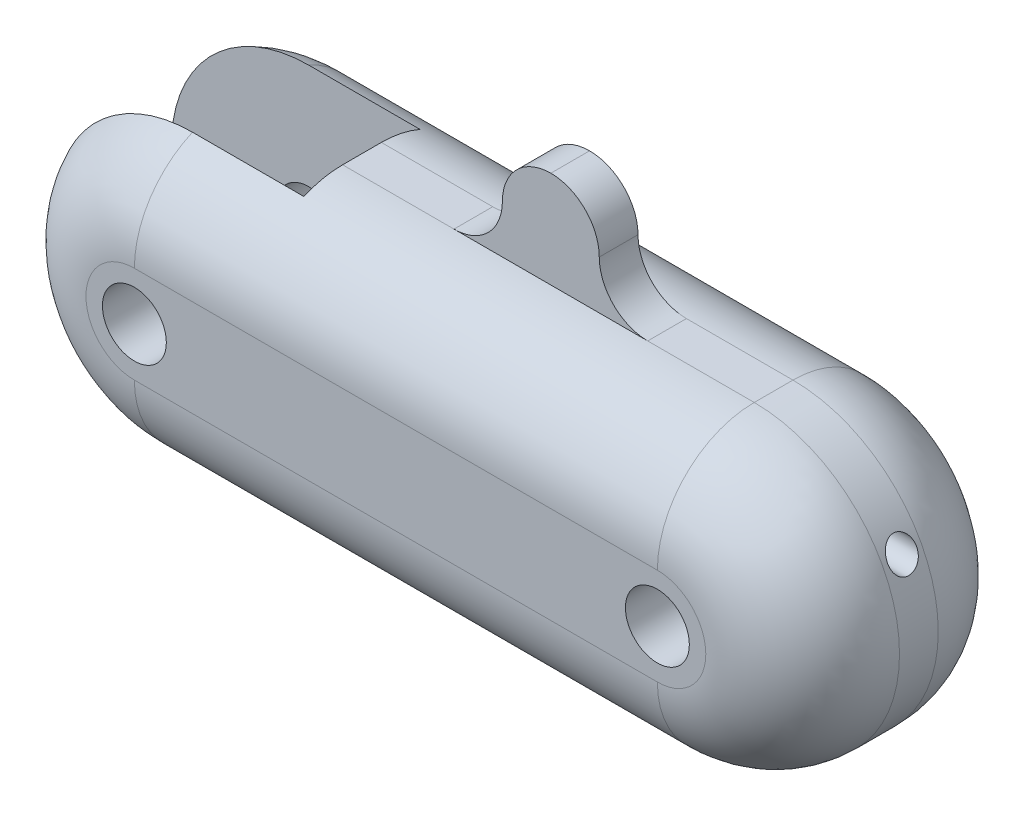
SolidWorks part; units mm, degrees
ref_plane "Front Plane" through (0, 0, 0) normal (0, 0, 1) x (1, 0, 0)
ref_plane "Top Plane" through (0, 0, 0) normal (0, 1, 0) x (1, 0, 0)
ref_plane "Right Plane" through (0, 0, 0) normal (1, 0, 0) x (0, 0, -1)
sketch "Sketch2" plane through (0, 0, 0) normal (0, 0, 1) x (1, 0, 0)
  line L0 (-13.5, 0) -> (13.5, 0)
  line L1 (-13.5, -15) -> (13.5, -15)
  arc A0 (-13.5, 0) -> (-13.5, -15) centre (-13.5, -7.5) ccw
  arc A1 (13.5, 0) -> (13.5, -15) centre (13.5, -7.5) cw
  point P4 (0, 0)
  dimension "D5" = 7.5
  dimension "D1" = 27
  dimension "D6" = 27
extrude "Boss-Extrude1" add sketch "Sketch2" along normal blind 12
fillet "Fillet1" radius 5 8 edges at (21, -7.5, 0) (0, -15, 0) (-21, -7.5, 0) (21, -7.5, 12) (0, -15, 12) (-21, -7.5, 12) (0, 0, 0) (0, 0, 12)
sketch "Sketch3" plane through (0, 0, 12) normal (0, 0, 1) x (1, 0, 0)
  circle A0 centre (-13.5, -7.5) radius 1.65
  circle A1 centre (13.5, -7.5) radius 1.65
  arc A4 (-13.5, -5) -> (-13.5, -10) centre (-13.5, -7.5) ccw construction
  point P11 (-16, -7.5)
  dimension "D1" = 3.3
ref_plane "Plane1" through (6, 0, 0) normal (-1, 0, 0) x (0, 0, 1)
ref_plane "Plane3" through (0, -25, 0) normal (0, -1, 0) x (-1, 0, 0)
sketch "Sketch5" plane through (0, -25, 0) normal (0, -1, 0) x (-1, 0, 0)
  line L0 (-13.5, 0) -> (13.5, 0) construction
  line L1 (7.75, -3) -> (21, -3)
  line L2 (7.75, -3) -> (7.75, -9)
  line L3 (7.75, -9) -> (21, -9)
  line L4 (21, -3) -> (21, -9)
  line L5 (13.5, -12) -> (-13.5, -12) construction
  line L7 (21, -7) -> (21, -5) construction
  dimension "D1" = 3
  dimension "D2" = 3
  dimension "D3" = 13.25
extrude "Cut-Extrude3" cut sketch "Sketch5" against normal through all
sketch "Sketch6" plane through (0, 0, 0) normal (0, 1, 0) x (1, 0, 0)
  line L0 (13.75, -12) -> (13.75, 0) construction
  line L1 (0.5, -5) -> (5.5, -5)
  line L2 (0.5, -5) -> (0.5, -7)
  line L3 (0.5, -7) -> (5.5, -7)
  line L4 (5.5, -5) -> (5.5, -7)
  line L5 (13.5, -7) -> (13.5, -12) construction
  line L6 (13.5, -5) -> (-7.75, -5) construction
  point P4 (5.5, -6)
  point P7 (13.75, -6)
  dimension "D1" = 5
  dimension "D3" = 8
extrude "Boss-Extrude2" add sketch "Sketch6" along normal blind 5
fillet "Fillet2" radius 2.5 2 edges at (5.5, 5, 6) (0.5, 5, 6)
fillet "Fillet3" radius 2.5 2 edges at (0.5, 0, 6) (5.5, 0, 6)
extrude "Cut-Extrude4" cut sketch "Sketch3" against normal through all
ref_plane "Plane4" through (21, 0, 0) normal (1, 0, 0) x (0, 0, -1)
sketch "Sketch8" plane through (21, 0, 0) normal (1, 0, 0) x (0, 0, -1)
  line L0 (-7, -15) -> (-5, -15) construction
  circle A0 centre (-6, -4) radius 0.75
  point P6 (-6, -15)
  dimension "D1" = 1.5
  dimension "D2" = 4
extrude "Cut-Extrude7" cut sketch "Sketch8" against normal through all
sketch "Sketch9" plane through (-7.75, 0, 0) normal (-1, 0, 0) x (0, 0, 1)
  line L1 (7, -15) -> (5, -15) construction
  circle A0 centre (6, -11) radius 0.75
  dimension "D1" = 1.5
  dimension "D2" = 4
sketch "Sketch10" plane through (0, -15, 0) normal (0, -1, 0) x (1, 0, 0)
  line L0 (13.5, 7) -> (13.5, 5) construction
  line L2 (13.5, 12) -> (13.5, 7) construction
  circle A0 centre (7.5, 6) radius 0.75
  point P5 (13.5, 6)
  point P10 (13.5, 9.5)
  dimension "D1" = 1.5
  dimension "D2" = 6
sketch "Sketch11" plane through (0, 0, 12) normal (0, 0, 1) x (1, 0, 0)
  line L0 (-7.75, -11) -> (7.5, -15) construction
  line L1 (-7.75, -10.25) -> (-7.75, -11.75) construction
  line L2 (6.75, -15) -> (8.25, -15) construction
extrude "Cut-Extrude9" cut sketch "Sketch9" along direction (0.9673, -0.2537, 0) on the side against the normal up to vertex (15.25 mm away) contours A0 up to point (7.5, -15, 6)
